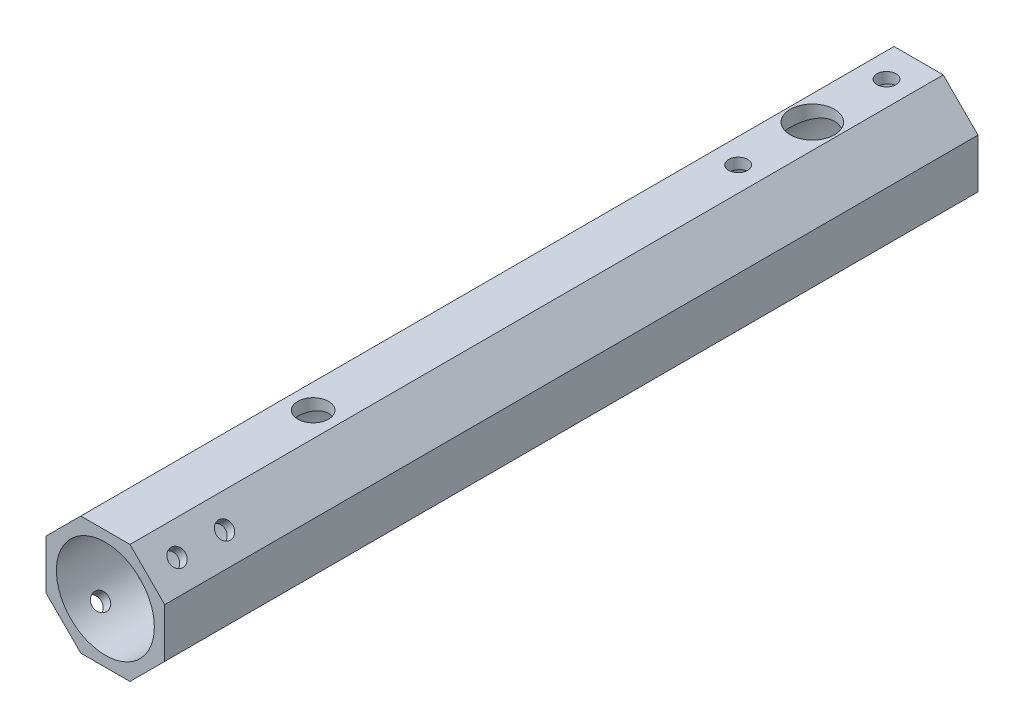
SolidWorks part; units mm, degrees
ref_plane "Front Plane" through (0, 0, 0) normal (0, 0, 1) x (1, 0, 0)
ref_plane "Top Plane" through (0, 0, 0) normal (0, 1, 0) x (1, 0, 0)
ref_plane "Right Plane" through (0, 0, 0) normal (1, 0, 0) x (0, 0, -1)
sketch "Sketch1" plane through (0, 0, 0) normal (0, 0, 1) x (1, 0, 0)
  line L6 (10, 4.1421) -> (4.1421, 10)
  line L7 (4.1421, 10) -> (-4.1421, 10)
  line L8 (-4.1421, 10) -> (-10, 4.1421)
  line L9 (-10, 4.1421) -> (-10, -4.1421)
  line L10 (-10, -4.1421) -> (-4.1421, -10)
  line L11 (-4.1421, -10) -> (4.1421, -10)
  line L12 (4.1421, -10) -> (10, -4.1421)
  line L13 (10, -4.1421) -> (10, 4.1421)
  circle A0 centre (0, 0) radius 8.25
  circle A1 centre (0, 0) radius 10 construction
  dimension "D1" = 16.5
  dimension "D2" = 20
extrude "Boss-Extrude1" add sketch "Sketch1" against normal up to surface (135 mm away)
sketch "Sketch2" plane through (0, 0, -135) normal (0, 0, -1) x (-1, 0, 0)
  line L8 (-10, 4.1421) -> (-10, -4.1421)
  line L9 (-10, -4.1421) -> (-4.1421, -10)
  line L10 (-4.1421, -10) -> (4.1421, -10)
  line L11 (4.1421, -10) -> (10, -4.1421)
  line L12 (10, -4.1421) -> (10, 4.1421)
  line L13 (10, 4.1421) -> (4.1421, 10)
  line L14 (4.1421, 10) -> (-4.1421, 10)
  line L15 (-4.1421, 10) -> (-10, 4.1421)
  line L16 (-10, 4.1421) -> (-10, -4.1421)
  line L17 (-10, -4.1421) -> (-4.1421, -10)
  line L18 (-4.1421, -10) -> (4.1421, -10)
  line L19 (4.1421, -10) -> (10, -4.1421)
  line L20 (10, -4.1421) -> (10, 4.1421)
  line L21 (10, 4.1421) -> (4.1421, 10)
  line L22 (4.1421, 10) -> (-4.1421, 10)
  line L23 (-4.1421, 10) -> (-10, 4.1421)
  dimension "D1" = 0
extrude "Boss-Extrude2" add sketch "Sketch2" along normal blind 2
sketch "Sketch4" plane through (0, 0, 0) normal (0, 1, 0) x (1, 0, 0)
  circle A0 centre (0, 131.5931) radius 1.6 construction
  circle A1 centre (0, 119.0931) radius 4.75 construction
  circle A2 centre (0, 106.5931) radius 1.6 construction
  circle A3 centre (0, 35) radius 2.6 construction
  circle A4 centre (0, 131.5931) radius 1.6
  circle A5 centre (0, 119.0931) radius 4.75 construction
  circle A6 centre (0, 106.5931) radius 1.6
  circle A7 centre (0, 35) radius 2.6
  circle A8 centre (0, 119.0931) radius 3.7279
extrude "Cut-Extrude1" cut sketch "Sketch4" against normal through all and the other way through all
sketch "Sketch6" plane through (-7.0711, 7.0711, 0) normal (-0.7071, 0.7071, 0) x (0, 0, 1)
  circle A0 centre (-13, 0) radius 1.4 construction
  circle A1 centre (-5, 0) radius 1.4 construction
  circle A2 centre (-13, 0) radius 1.4
  circle A3 centre (-5, 0) radius 1.4
extrude "Cut-Extrude2" cut sketch "Sketch6" against normal through all
ref_axis "Axis1" through (0, 0, 6.85) along (0, 0, -1)
pattern_circular "CirPattern1" count 2 every 270 about axis through (0, 0, 6.85) along (0, 0, -1) of "Cut-Extrude2"
sketch "Sketch7" plane through (0, 0, -137) normal (0, 0, -1) x (-1, 0, 0)
  circle A0 centre (0, 0) radius 6.2698
extrude "Cut-Extrude3" cut sketch "Sketch7" against normal through all
